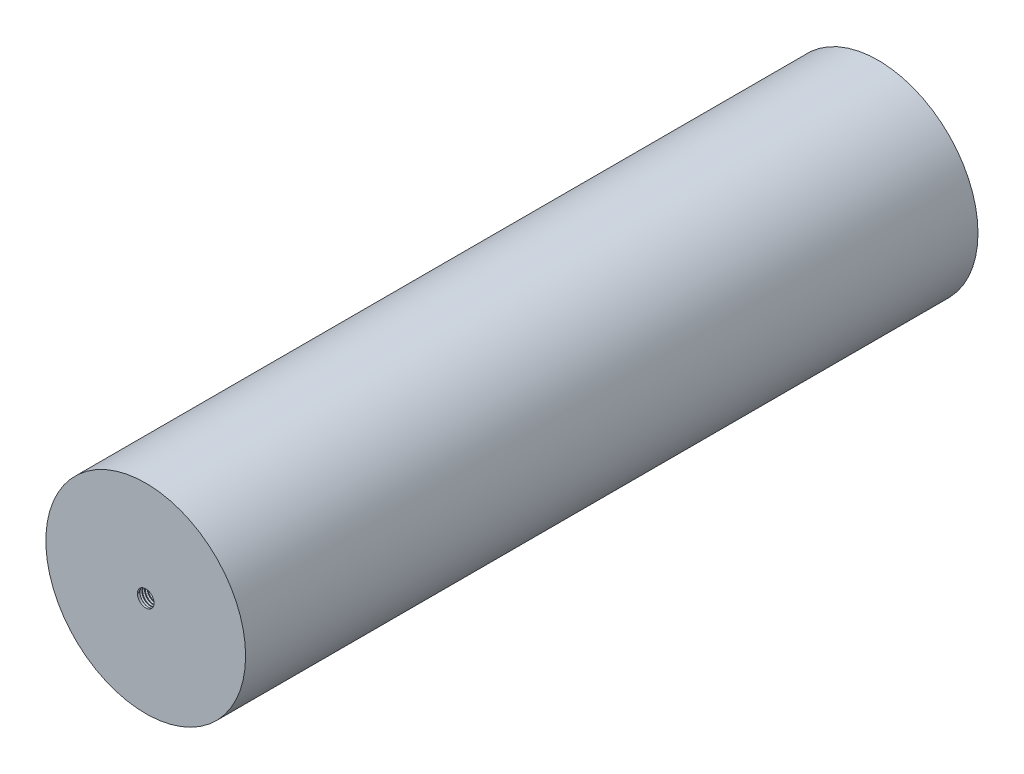
SolidWorks part; units mm, degrees
ref_plane "Front Plane" through (0, 0, 0) normal (0, 0, 1) x (1, 0, 0)
ref_plane "Top Plane" through (0, 0, 0) normal (0, 1, 0) x (1, 0, 0)
ref_plane "Right Plane" through (0, 0, 0) normal (1, 0, 0) x (0, 0, -1)
sketch "Sketch1" plane through (0, 0, 0) normal (0, 0, 1) x (1, 0, 0)
  circle A0 centre (0, 0) radius 38.1
  dimension "D1" = 76.2
extrude "Boss-Extrude1" add sketch "Sketch1" along normal blind 139.7 and the other way blind 139.7
sketch "Sketch2" plane through (0, 0, 139.7) normal (0, 0, 1) x (1, 0, 0)
  circle A0 centre (0, 0) radius 3.175
  dimension "D1" = 6.35
extrude "Cut-Extrude1" cut sketch "Sketch2" against normal blind 20
thread "Thread1" pitch 1 method cut profile "Thread Profile2" start angle 0, offset 0, length 20, pitch 1, diameter 6.35
ref_plane "Plane2" through (-3.175, 0, 139.7) normal (0, -1, 0) x (-1, 0, 0)
sketch "Thread Profile2" plane through (-3.175, 0, 139.7) normal (0, -1, 0) x (-1, 0, 0)
  line L0 (0, 0) -> (0, 1) construction
  line L1 (0, 0) -> (0.5413, 0.3125)
  line L2 (0.5413, 0.3125) -> (0.5413, 0.4375)
  line L3 (0.5413, 0.4375) -> (0, 0.75)
  line L4 (0.5413, 0.375) -> (0, 0.375) construction
  line L11 (0, 0) -> (0, 0.75)
  point P2 (0, 0)
  dimension "Pitch" = 1
  dimension "Profile_Angle" = 60
  dimension "Profile_Land" = 0.125
  dimension "Profile_Height" = 0.5413
sketch "Sketch8" plane through (0, 0, -139.7) normal (0, 0, -1) x (-1, 0, 0)
  circle A0 centre (0, 0) radius 3.175
  dimension "D1" = 6.35
extrude "Cut-Extrude2" cut sketch "Sketch8" against normal blind 20
thread "Thread2" pitch 1 method cut profile "Thread Profile3" start angle 0, offset 0, length 20, pitch 1, diameter 6.35
ref_plane "Plane3" through (3.175, 0, -139.7) normal (0, -1, 0) x (1, 0, 0)
sketch "Thread Profile3" plane through (3.175, 0, -139.7) normal (0, -1, 0) x (1, 0, 0)
  line L0 (0, 0) -> (0, 1) construction
  line L1 (0, 0) -> (0.5413, 0.3125)
  line L2 (0.5413, 0.3125) -> (0.5413, 0.4375)
  line L3 (0.5413, 0.4375) -> (0, 0.75)
  line L4 (0.5413, 0.375) -> (0, 0.375) construction
  line L11 (0, 0) -> (0, 0.75)
  point P2 (0, 0)
  dimension "Pitch" = 1
  dimension "Profile_Angle" = 60
  dimension "Profile_Land" = 0.125
  dimension "Profile_Height" = 0.5413
